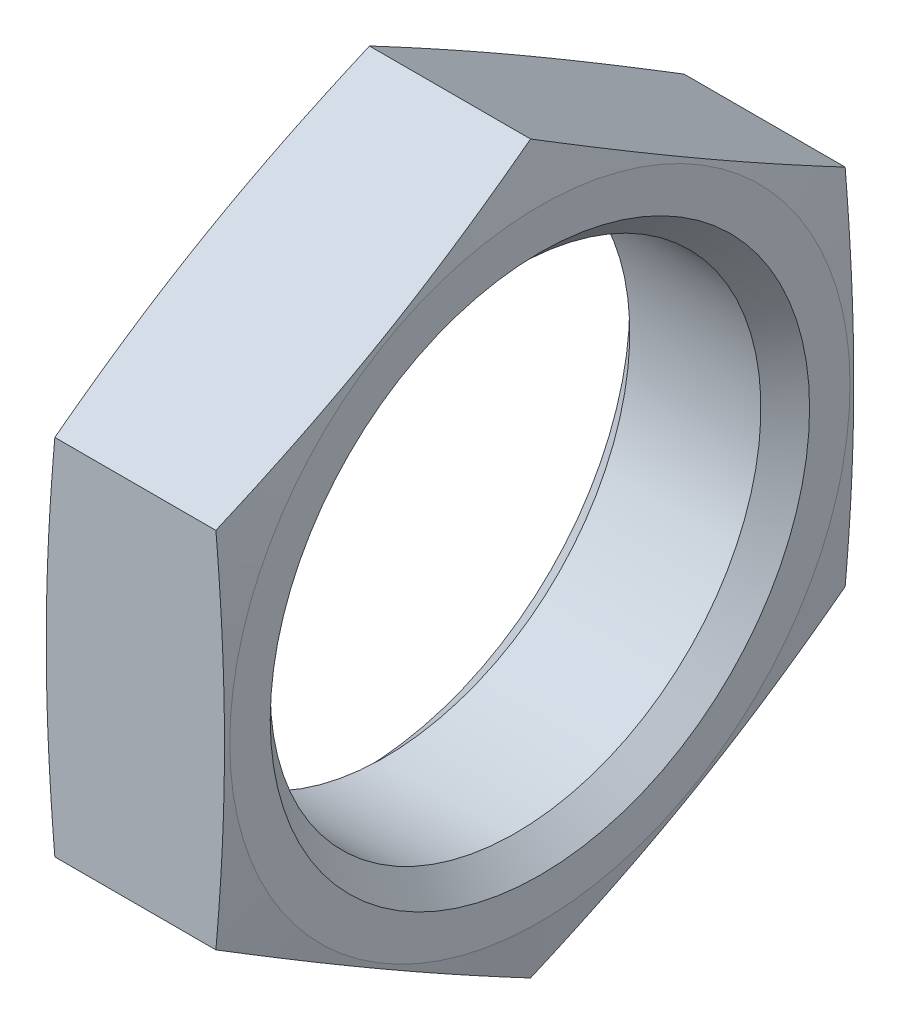
SolidWorks part; units mm, degrees
ref_plane "Front Plane" through (0, 0, 0) normal (0, 0, 1) x (1, 0, 0)
ref_plane "Top Plane" through (0, 0, 0) normal (0, 1, 0) x (1, 0, 0)
ref_plane "Right Plane" through (0, 0, 0) normal (1, 0, 0) x (0, 0, -1)
sketch "Sketch1" plane through (0, 0, 0) normal (0, 0, 1) x (1, 0, 0)
  line L0 (0, 0) -> (0, 6.9)
  line L1 (0, 6.9) -> (0.5113, 9.8)
  line L2 (0.5113, 9.8) -> (3.4887, 9.8)
  line L3 (3.4887, 9.8) -> (4, 6.9)
  line L4 (4, 6.9) -> (4, 0)
  line L5 (4, 0) -> (0, 0)
  line L6 (4, 0) -> (0, 0) construction
revolve "Revolve1" add sketch "Sketch1" angle 360 about L6 reverse direction yes
sketch "Sketch2" plane through (0, 0, 0) normal (0, 0, 1) x (1, 0, 0)
  line L0 (0, 0) -> (0, 6)
  line L1 (0, 6) -> (0.5415, 5.4585)
  line L2 (0.5415, 5.4585) -> (3.4585, 5.4585)
  line L3 (3.4585, 5.4585) -> (4, 6)
  line L4 (4, 6) -> (4, 0)
  line L5 (4, 0) -> (0, 0)
  line L6 (4, 0) -> (0, 0) construction
revolve "Cut-Revolve1" cut sketch "Sketch2" angle 360 about L6 reverse direction yes
cosmetic thread "Cosmetic Thread1" parameters "D1"=4, "D2"=12
sketch "Sketch3" plane through (0, 0, 0) normal (1, 0, 0) x (0, 0, -1)
  line L0 (-14, 14) -> (-14, -14)
  line L1 (-14, -14) -> (14, -14)
  line L2 (14, -14) -> (14, 14)
  line L3 (14, 14) -> (-14, 14)
  line L4 (-7, -4.0415) -> (0, -8.0829)
  line L5 (0, -8.0829) -> (7, -4.0415)
  line L6 (7, -4.0415) -> (7, 4.0415)
  line L7 (7, 4.0415) -> (0, 8.0829)
  line L8 (0, 8.0829) -> (-7, 4.0415)
  line L9 (-7, 4.0415) -> (-7, -4.0415)
extrude "Cut-Extrude1" cut sketch "Sketch3" along normal blind 4
ref_plane "ANBAU XY" through (0, 0, 0) normal (1, 0, 0) x (0, 0, -1)
ref_plane "ANBAU XZ" through (0, 0, 0) normal (0, -1, 0) x (-1, 0, 0)
ref_plane "ANBAU YZ" through (0, 0, 0) normal (0, 0, -1) x (-1, 0, 0)
ref_axis "ANBAU X" through (0, 0, 80.9) along (0, 0, -1)
ref_axis "ANBAU Y" through (0, -50, 0) along (0, 1, 0)
ref_axis "ANBAU Z" through (80.9, 0, 0) along (-1, 0, 0)
sketch3d "ANBAU"
  point P0 (0, 0, 0)
ref_plane "SLE XY" through (4, 0, 0) normal (-1, 0, 0) x (0, 0, 1)
ref_plane "SLE XZ" through (0, 0, 0) normal (0, 0, 1) x (1, 0, 0)
ref_plane "SLE YZ" through (0, 0, 0) normal (0, 1, 0) x (1, 0, 0)
ref_axis "SLE X" through (4, -50, 0) along (0, 1, 0)
ref_axis "SLE Y" through (4, 0, 80.9) along (0, 0, -1)
ref_axis "SLE Z" through (-80.9, 0, 0) along (1, 0, 0)
sketch3d "SLE"
  point P0 (4, 0, 0)
